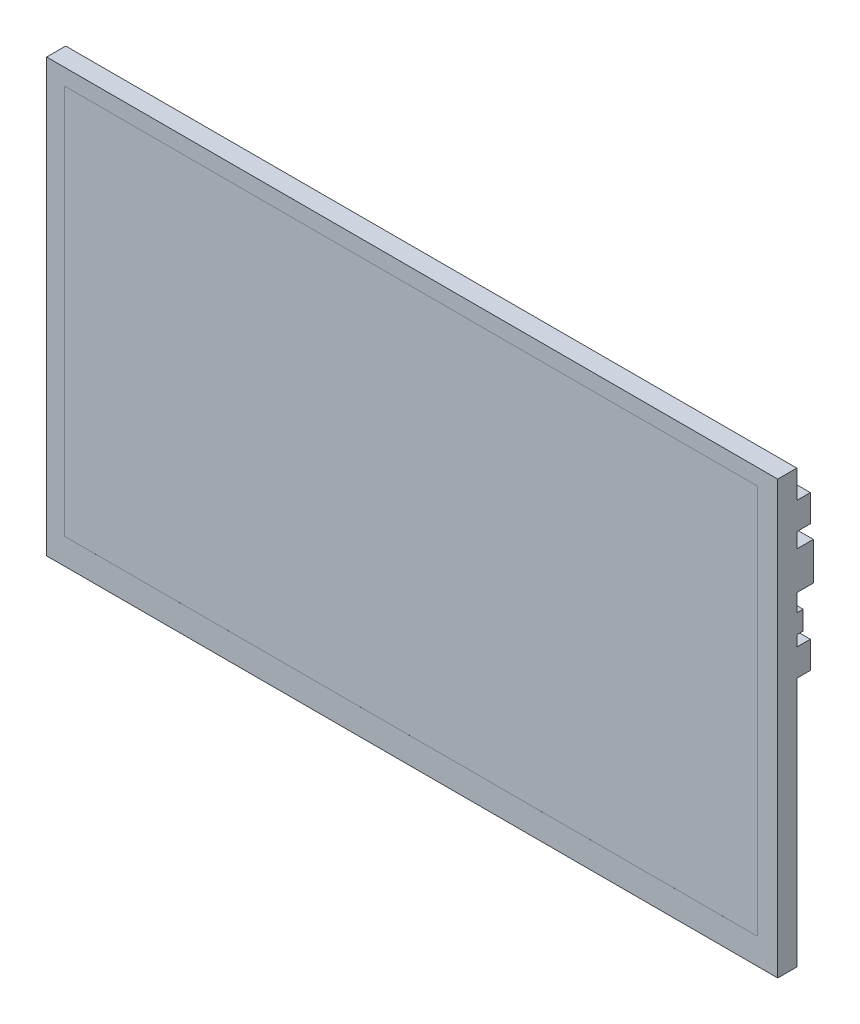
SolidWorks part; units mm, degrees
ref_plane "Front Plane" through (0, 0, 0) normal (0, 0, 1) x (1, 0, 0)
ref_plane "Top Plane" through (0, 0, 0) normal (0, 1, 0) x (1, 0, 0)
ref_plane "Right Plane" through (0, 0, 0) normal (1, 0, 0) x (0, 0, -1)
sketch "Sketch1" plane through (0, 0, 0) normal (0, 0, 1) x (1, 0, 0)
  line L1 (135.185, -79.895) -> (-135.185, -79.895)
  line L2 (135.185, -79.895) -> (135.185, 79.895)
  line L3 (135.185, 79.895) -> (-135.185, 79.895)
  line L4 (-135.185, -79.895) -> (-135.185, 79.895)
  line L5 (135.185, -79.895) -> (-135.185, 79.895) construction
  line L6 (135.185, 79.895) -> (-135.185, -79.895) construction
  point P0 (0, 0)
  dimension "D1" = 270.37
  dimension "D2" = 159.79
extrude "Boss-Extrude1" add sketch "Sketch1" against normal blind 7.05
sketch "Sketch2" plane through (0, 0, 0) normal (0, 0, 1) x (1, 0, 0)
  line L0 (-135.185, 79.895) -> (-135.185, -79.895) construction
  line L1 (127.735, -70.285) -> (-128.585, -70.285)
  line L2 (127.735, -70.285) -> (127.735, 73.895)
  line L3 (127.735, 73.895) -> (-128.585, 73.895)
  line L4 (-128.585, -70.285) -> (-128.585, 73.895)
  line L5 (127.735, -70.285) -> (-128.585, 73.895) construction
  line L6 (127.735, 73.895) -> (-128.585, -70.285) construction
  line L7 (135.185, 79.895) -> (-135.185, 79.895) construction
  point P0 (-0.425, 1.805)
  dimension "D1" = 134.76
  dimension "D2" = 78.09
  dimension "D3" = 144.18
  dimension "D4" = 256.32
extrude "Cut-Extrude1" cut sketch "Sketch2" against normal blind 0.001
sketch "Sketch3" plane through (0, 0, -7.05) normal (0, 0, -1) x (-1, 0, 0)
  line L0 (-135.185, -79.895) -> (-135.185, 79.895) construction
  line L1 (-135.185, 69.545) -> (-110.185, 69.545)
  line L2 (-135.185, 69.545) -> (-135.185, 59.545)
  line L3 (-135.185, 59.545) -> (-110.185, 59.545)
  line L4 (-110.185, 69.545) -> (-110.185, 59.545)
  line L5 (-135.185, 69.545) -> (-110.185, 59.545) construction
  line L6 (-135.185, 59.545) -> (-110.185, 69.545) construction
  line L7 (-135.185, 79.895) -> (135.185, 79.895) construction
  line L9 (-110.185, 40.005) -> (-135.185, 40.005)
  line L10 (-110.185, 40.005) -> (-110.185, 54.005)
  line L11 (-110.185, 54.005) -> (-135.185, 54.005)
  line L12 (-135.185, 40.005) -> (-135.185, 54.005)
  line L13 (-110.185, 40.005) -> (-135.185, 54.005) construction
  line L14 (-110.185, 54.005) -> (-135.185, 40.005) construction
  line L15 (-110.185, 26.525) -> (-135.185, 26.525)
  line L16 (-110.185, 26.525) -> (-110.185, 33.525)
  line L17 (-110.185, 33.525) -> (-135.185, 33.525)
  line L18 (-135.185, 26.525) -> (-135.185, 33.525)
  line L19 (-110.185, 26.525) -> (-135.185, 33.525) construction
  line L20 (-110.185, 33.525) -> (-135.185, 26.525) construction
  line L21 (-110.185, 12.585) -> (-135.185, 12.585)
  line L22 (-110.185, 12.585) -> (-110.185, 22.585)
  line L23 (-110.185, 22.585) -> (-135.185, 22.585)
  line L24 (-135.185, 12.585) -> (-135.185, 22.585)
  line L25 (-110.185, 12.585) -> (-135.185, 22.585) construction
  line L26 (-110.185, 22.585) -> (-135.185, 12.585) construction
  point P4 (-122.685, 64.545)
  point P9 (-122.685, 47.005)
  point P14 (-122.685, 30.025)
  point P19 (-122.685, 17.585)
  point P24 (0, 0)
  line M7 (-135.185, 79.895) -> (-135.185, -79.895)
  dimension "D1" = 15.35
  dimension "D2" = 25
  dimension "D3" = 10
  dimension "D4" = 17.54
  dimension "D5" = 16.98
  dimension "D6" = 12.44
  dimension "D7" = 14
  dimension "D8" = 7
  dimension "D9" = 10
extrude "Boss-Extrude3" add sketch "Sketch3" along normal blind 5 contours L4 L1 L3 M7 region at (122.685, 64.545, -7.05)
extrude "Boss-Extrude4" add sketch "Sketch3<3>" along normal blind 6.12 contours L9 L12 L11 L10
sketch "Sketch3<3>" plane through (0, 0, -7.05) normal (0, 0, -1) x (-1, 0, 0) same geometry as "Sketch3"
extrude "Boss-Extrude5" add sketch "Sketch3<4>" along normal blind 2.35 contours L15 L18 L17 L16
sketch "Sketch3<4>" plane through (0, 0, -7.05) normal (0, 0, -1) x (-1, 0, 0) same geometry as "Sketch3"
extrude "Boss-Extrude6" add sketch "Sketch3<5>" along normal blind 5 contours L22 L23 L21 M7 region at (122.685, 17.585, -7.05)
sketch "Sketch3<5>" plane through (0, 0, -7.05) normal (0, 0, -1) x (-1, 0, 0) same geometry as "Sketch3"
sketch "Sketch5" plane through (0, 0, -13.17) normal (0, 0, -1) x (-1, 0, 0)
  text T0 "AUDIO"
  text T1 "HDMI"
  text T2 "USB"
  text T3 "POWER"
  text T4 "-"
  text T5 "+"
split line "Split Line1"
